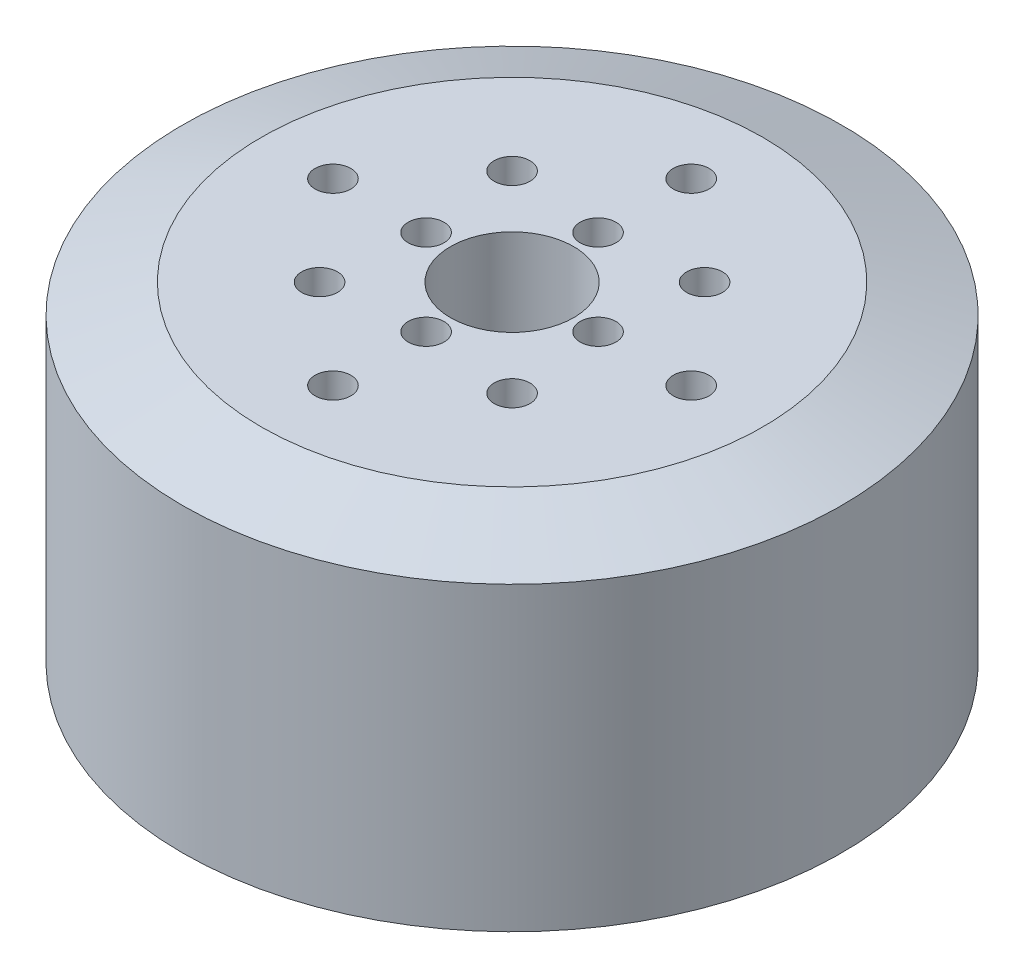
SolidWorks part; units mm, degrees
material "Латунь"
ref_plane "Спереди" through (0, 0, 0) normal (0, 0, 1) x (1, 0, 0)
ref_plane "Сверху" through (0, 0, 0) normal (0, 1, 0) x (1, 0, 0)
ref_plane "Справа" through (0, 0, 0) normal (1, 0, 0) x (0, 0, -1)
sketch "Эскиз1" plane through (0, 0, 0) normal (0, 1, 0) x (1, 0, 0)
  circle A0 centre (0, 0) radius 23
  dimension "D1" = 46
extrude "Бобышка-Вытянуть1" add sketch "Эскиз1" along normal blind 23
chamfer "Фаска1" distance 2 angle 70 1 edges at (0, 23, 23) first distance on face at (0, 23, 23)
sketch "Эскиз2" plane through (0, 23, 0) normal (0, 1, 0) x (1, 0, 0)
  circle A0 centre (0, 0) radius 3.5
  circle A1 centre (0, 0) radius 5
  dimension "D1" = 7
  dimension "D2" = 10
extrude "Вырез-Вытянуть1" cut sketch "Эскиз2" against normal through all contours A0 region at (0, 23, 0)
extrude "Бобышка-Вытянуть2" add sketch "Эскиз2<3>" against normal blind 32
sketch "Эскиз2<3>" plane through (0, 23, 0) normal (0, 1, 0) x (1, 0, 0) same geometry as "Эскиз2"
sketch "Эскиз3" plane through (0, 23, 0) normal (0, 1, 0) x (1, 0, 0)
  line L0 (9.5, 0) -> (0, 0) construction
  line L1 (0, 0) -> (6.7175, 6.7175) construction
  line L2 (0, 0) -> (6.7175, -6.7175) construction
  line L3 (0, 0) -> (-6.7175, -6.7175) construction
  line L4 (0, 0) -> (-6.7175, 6.7175) construction
  circle A0 centre (0, 0) radius 6 construction
  circle A1 centre (0, 0) radius 12.5 construction
  circle A2 centre (0, 0) radius 9.5 construction
  point P4 (0, 12.5)
  point P5 (0, -12.5)
  point P6 (-12.5, 0)
  point P7 (12.5, 0)
  point P8 (6, 0)
  point P9 (0, 6)
  point P10 (-6, 0)
  point P11 (0, -6)
  point P21 (0, 0)
  dimension "D1" = 12
  dimension "D2" = 25
  dimension "D3" = 19
  dimension "D4" = 45
  dimension "D5" = 4
sketch "Эскиз4" plane through (0, 0, 0) normal (0, -1, 0) x (1, 0, 0)
  circle A1 centre (0, 0) radius 5 construction
  circle A2 centre (0, 0) radius 21
  circle A3 centre (0, 0) radius 21
  circle A4 centre (0, 0) radius 5
  dimension "D1" = 2
extrude "Вырез-Вытянуть2" cut sketch "Эскиз4" against normal blind 19
hole_wizard "Отверстие обработанное метчиком M3x0.51" positions "Эскиз6" profile "Эскиз5" tap size "M3x0.5" standard "Ansi Metric" end condition through all
sketch "Эскиз6" plane through (0, 23, 0) normal (0, 1, 0) x (1, 0, 0)
  point P0 (0, 12.5)
  point P3 (12.5, 0)
  point P6 (0, -12.5)
  point P9 (-12.5, 0)
sketch "Эскиз5" plane through (0, 23, -12.5) normal (1, 0, 0) x (0, 0, 1)
  line L0 (0, 0) -> (0, 32)
  line L1 (0, 32) -> (1.25, 32)
  line L2 (1.25, 32) -> (1.25, 0)
  line L5 (1.25, 0) -> (0, 0)
  line L11 (0, -6.35) -> (0, 107.95) construction
  dimension "Диаметр проходного сверла" = 2.5
  dimension "Глубина проходного сверла" = 32
cosmetic thread "Отверстие резьбы1" parameters "D2"=3
cosmetic thread "Отверстие резьбы2" parameters "D2"=3
cosmetic thread "Отверстие резьбы3" parameters "D2"=3
cosmetic thread "Отверстие резьбы4" parameters "D2"=3
hole_wizard "Отверстие обработанное метчиком M3x0.52" positions "Эскиз8" profile "Эскиз7" tap size "M3x0.5" standard "Ansi Metric"
sketch "Эскиз8" plane through (0, 23, 0) normal (0, 1, 0) x (1, 0, 0)
  point P0 (6, 0)
  point P2 (0, 6)
  point P5 (-6, 0)
  point P8 (0, -6)
cosmetic thread "Отверстие резьбы5" parameters "D1"=6, "D2"=3
cosmetic thread "Отверстие резьбы6" parameters "D1"=6, "D2"=3
cosmetic thread "Отверстие резьбы7" parameters "D1"=6, "D2"=3
cosmetic thread "Отверстие резьбы8" parameters "D1"=6, "D2"=3
sketch "Эскиз7" plane through (6, 23, 0) normal (1, 0, 0) x (0, 0, 1)
  line L0 (0, 0) -> (0, 8.2511)
  line L1 (0, 8.2511) -> (1.25, 7.5)
  line L2 (1.25, 7.5) -> (1.25, 0)
  line L5 (1.25, 0) -> (0, 0)
  line L10 (0, 8.2511) -> (-1.25, 7.5) construction
  line L11 (0, -6.35) -> (0, 107.95) construction
  dimension "Диаметр сверла" = 2.5
  dimension "Глубина сверла" = 7.5
  dimension "Угол заточки сверла" = 118
sketch "Эскиз9" plane through (0, 23, 0) normal (0, 1, 0) x (1, 0, 0)
  point P3 (0, -6)
  point P5 (6, 0)
hole_wizard "Отверстие обработанное метчиком M3x0.53" positions "Эскиз11" profile "Эскиз10" tap size "M3x0.5" standard "Ansi Metric" end condition through all
sketch "Эскиз11" plane through (0, 23, 0) normal (0, 1, 0) x (1, 0, 0)
  point P0 (-6.7175, 6.7175)
  point P3 (6.7175, 6.7175)
  point P6 (6.7175, -6.7175)
  point P9 (-6.7175, -6.7175)
cosmetic thread "Отверстие резьбы9" parameters "D2"=3
cosmetic thread "Отверстие резьбы10" parameters "D2"=3
cosmetic thread "Отверстие резьбы11" parameters "D2"=3
cosmetic thread "Отверстие резьбы12" parameters "D2"=3
sketch "Эскиз10" plane through (-6.7175, 23, -6.7175) normal (1, 0, 0) x (0, 0, 1)
  line L0 (0, 0) -> (0, 32)
  line L1 (0, 32) -> (1.25, 32)
  line L2 (1.25, 32) -> (1.25, 0)
  line L5 (1.25, 0) -> (0, 0)
  line L11 (0, -6.35) -> (0, 107.95) construction
  dimension "Диаметр проходного сверла" = 2.5
  dimension "Глубина проходного сверла" = 32
sketch "Эскиз12" plane through (0, 23, 0) normal (0, 1, 0) x (1, 0, 0)
  circle A0 centre (0, 0) radius 4.3
  dimension "D1" = 8.6
extrude "Вырез-Вытянуть3" cut sketch "Эскиз12" against normal blind 25
sketch "Эскиз13" plane through (0, 23, 0) normal (0, 1, 0) x (1, 0, 0)
  line L1 (-7.2175, 7.2175) -> (-6.2175, 7.2175)
  line L2 (-7.2175, 7.2175) -> (-7.2175, 6.2175)
  line L3 (-7.2175, 6.2175) -> (-6.2175, 6.2175)
  line L4 (-6.2175, 7.2175) -> (-6.2175, 6.2175)
  line L5 (-7.2175, 7.2175) -> (-6.2175, 6.2175) construction
  line L6 (-7.2175, 6.2175) -> (-6.2175, 7.2175) construction
  point P0 (-6.7175, 6.7175)
  point P1 (6.7175, 6.7175)
  point P3 (6.7175, -6.7175)
  point P5 (-6.7175, 6.7175)
  dimension "D1" = 1
ref_plane "Плоскость1" through (0, 5, 0) normal (0, -1, 0) x (-1, 0, 0)
equation "\"D2@Эскиз2\"=\"D1@Эскиз2\"+3"
